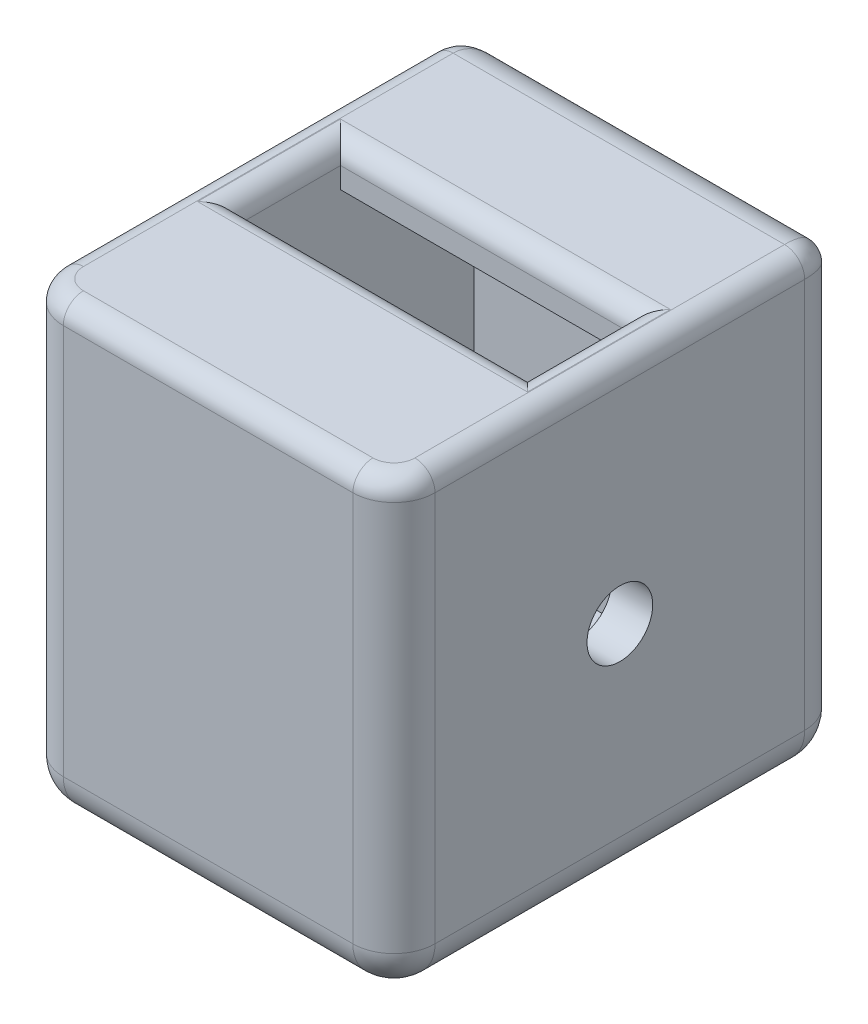
SolidWorks part; units mm, degrees
material "POLYURETHANE (11671)"
ref_plane "Front Plane" through (0, 0, 0) normal (0, 0, 1) x (1, 0, 0)
ref_plane "Top Plane" through (0, 0, 0) normal (0, 1, 0) x (1, 0, 0)
ref_plane "Right Plane" through (0, 0, 0) normal (1, 0, 0) x (0, 0, -1)
sketch "Sketch2" plane through (0, 0, 0) normal (0, 1, 0) x (1, 0, 0)
  line L0 (-8.9535, 11.43) -> (-8.9535, 13.97) construction
  line L1 (8.9535, 11.43) -> (-8.9535, 11.43)
  line L2 (8.9535, 11.43) -> (8.9535, -11.43)
  line L3 (8.9535, -11.43) -> (-8.9535, -11.43)
  line L4 (-8.9535, 11.43) -> (-8.9535, -11.43)
  line L5 (11.4935, 13.97) -> (-11.4935, 13.97)
  line L6 (11.4935, 13.97) -> (11.4935, -13.97)
  line L7 (11.4935, -13.97) -> (-11.4935, -13.97)
  line L8 (-11.4935, 13.97) -> (-11.4935, -13.97)
  line L9 (-8.9535, 11.43) -> (-11.4935, 11.43) construction
  point P8 (0, 13.97)
  point P9 (0, 11.43)
  point P11 (-8.9535, 0)
  point P12 (-11.4935, 0)
  dimension "D1" = 17.907
  dimension "D2" = 22.86
  dimension "D3" = 2.54
extrude "Boss-Extrude1" add sketch "Sketch2" along normal mid plane 27.94
sketch "Sketch3" plane through (0, -13.97, 0) normal (0, -1, 0) x (1, 0, 0)
  line L1 (-8.9535, 11.43) -> (8.9535, 11.43)
  line L2 (-8.9535, 11.43) -> (-8.9535, -11.43)
  line L3 (-8.9535, -11.43) -> (8.9535, -11.43)
  line L4 (8.9535, 11.43) -> (8.9535, -11.43)
extrude "Boss-Extrude2" add sketch "Sketch3" against normal blind 2.54
sketch "Sketch4" plane through (0, 13.97, 0) normal (0, 1, 0) x (1, 0, 0)
  line L0 (8.9535, -11.43) -> (8.9535, 11.43) construction
  line L1 (-8.9535, 11.43) -> (8.9535, 11.43)
  line L2 (-8.9535, 11.43) -> (-8.9535, 3.175)
  line L3 (-8.9535, 3.175) -> (8.9535, 3.175)
  line L4 (8.9535, 11.43) -> (8.9535, 3.175)
  line L11 (-8.9535, -11.43) -> (8.9535, -11.43) construction
  line L12 (-8.9535, -11.43) -> (8.9535, -11.43)
  line L13 (-8.9535, -11.43) -> (-8.9535, -3.175)
  line L14 (-8.9535, -3.175) -> (8.9535, -3.175)
  line L15 (8.9535, -11.43) -> (8.9535, -3.175)
  line L16 (8.9535, -11.43) -> (-8.9535, -11.43) construction
  dimension "D1" = 6.35
extrude "Boss-Extrude3" add sketch "Sketch4" against normal blind 2.54
sketch "Sketch5" plane through (-11.4935, 0, 0) normal (-1, 0, 0) x (0, 0, 1)
  line L1 (-13.97, -13.97) -> (13.97, -13.97)
  line L2 (-13.97, -13.97) -> (-13.97, 13.97)
  line L3 (-13.97, 13.97) -> (13.97, 13.97)
  line L4 (13.97, -13.97) -> (13.97, 13.97)
  line L5 (-13.97, -13.97) -> (13.97, 13.97) construction
  line L6 (-13.97, 13.97) -> (13.97, -13.97) construction
  circle A0 centre (0, 0) radius 10.033
  point P0 (0, 0)
  dimension "D1" = 20.066
extrude "Cut-Extrude1" [suppressed] cut sketch "Sketch5" against normal up to surface (2.54 mm away) contours A0 up to face at (-8.9535, 6.35, 0)
sketch "Sketch6" plane through (11.4935, 0, 0) normal (1, 0, 0) x (0, 0, -1)
  line L1 (-13.97, -13.97) -> (13.97, -13.97)
  line L2 (-13.97, -13.97) -> (-13.97, 13.97)
  line L3 (-13.97, 13.97) -> (13.97, 13.97)
  line L4 (13.97, -13.97) -> (13.97, 13.97)
  line L5 (-13.97, -13.97) -> (13.97, 13.97) construction
  line L6 (-13.97, 13.97) -> (13.97, -13.97) construction
  circle A0 centre (0, 0) radius 2.032
  point P0 (0, 0)
  dimension "D1" = 4.064
extrude "Cut-Extrude2" cut sketch "Sketch6" against normal up to surface (2.54 mm away) contours A0 region at (11.4935, 0, 0) up to face at (8.9535, 6.35, 0)
sketch "Sketch7" plane through (0, 0, -13.97) normal (0, 0, -1) x (-1, 0, 0)
  line L0 (-11.4935, 13.97) -> (-11.4935, -13.97) construction
  line L1 (-5.7785, -3.175) -> (-2.6035, -3.175)
  line L2 (-5.7785, -3.175) -> (-5.7785, 3.175)
  line L3 (-5.7785, 3.175) -> (-2.6035, 3.175)
  line L4 (-2.6035, -3.175) -> (-2.6035, 3.175)
  line L5 (-5.7785, -3.175) -> (-2.6035, 3.175) construction
  line L6 (-5.7785, 3.175) -> (-2.6035, -3.175) construction
  point P0 (-4.191, 0)
  dimension "D1" = 3.175
  dimension "D2" = 5.715
  dimension "D3" = 6.35
extrude "Cut-Extrude3" cut sketch "Sketch7" against normal up to surface (2.54 mm away) contours L4 L3 L2 L1 up to face at (0, 0, -11.43)
sketch "Sketch10" [suppressed] plane through (0, 0, 13.97) normal (0, 0, 1) x (1, 0, 0)
  line L0 (10.16, 13.97) -> (10.16, -13.97) construction
  line L1 (1.27, -3.175) -> (4.445, -3.175)
  line L2 (1.27, -3.175) -> (1.27, 3.175)
  line L3 (1.27, 3.175) -> (4.445, 3.175)
  line L4 (4.445, -3.175) -> (4.445, 3.175)
  line L5 (1.27, -3.175) -> (4.445, 3.175) construction
  line L6 (1.27, 3.175) -> (4.445, -3.175) construction
  point P0 (2.8575, 0)
  dimension "D1" = 5.715
  dimension "D2" = 3.175
  dimension "D3" = 6.35
extrude "Cut-Extrude4" [suppressed] cut sketch "Sketch10" against normal up to next
fillet "Fillet1" radius 2.54 9 edges at (-11.4935, 0, -13.97) (-11.4935, 0, 13.97) (11.4935, 0, -13.97) (11.4935, 0, 13.97) (0, 13.97, -13.97) (-11.4935, -13.97, 0) (11.4935, -13.97, 0) (0, -13.97, 13.97) (0, -13.97, -13.97)
fillet "Fillet2" radius 1.2446 11 edges at (-10.7496, 13.2261, -13.2261) (-11.4935, 13.97, 0) (-10.7496, 13.97, 13.2261) (0, 13.97, 13.97) (10.7496, 13.97, 13.2261) (10.7496, 13.2261, -13.2261) (-8.9535, 13.97, 0) (8.9535, 13.97, 0) (0, 13.97, -3.175) (11.4935, 13.97, 0) (0, 13.97, 3.175)
